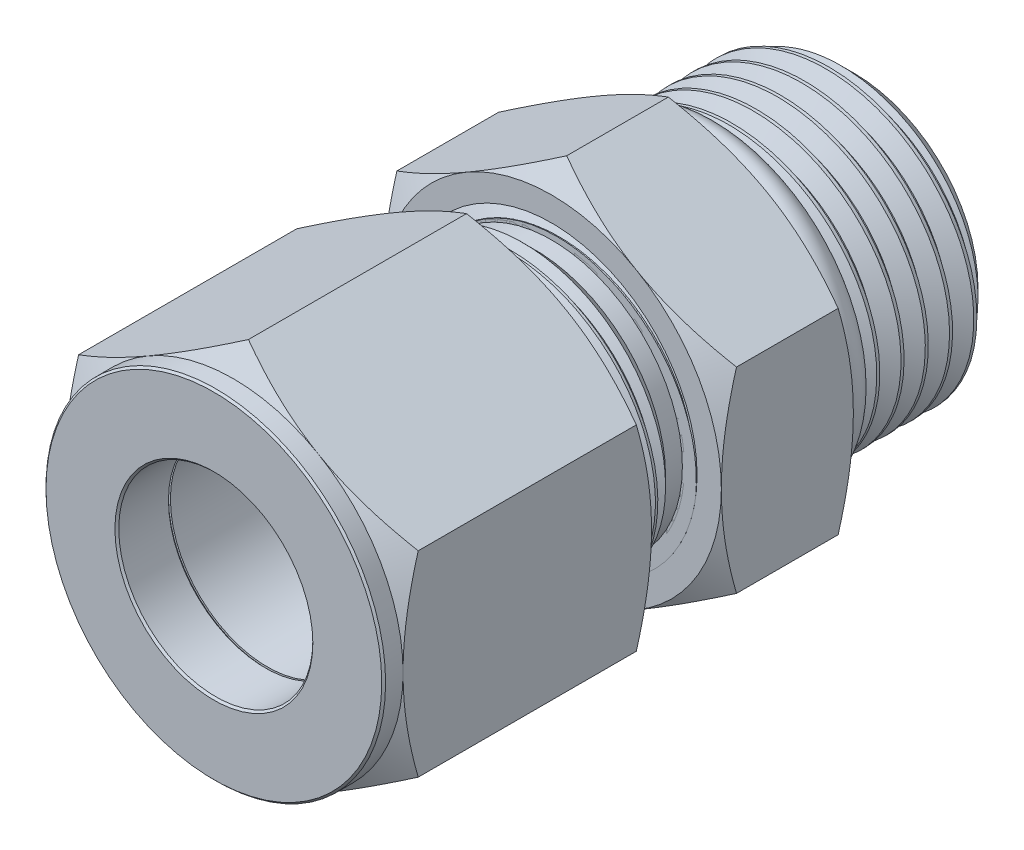
SolidWorks part; units mm, degrees
note: '?' marks a value the reader was unsure of.
material "AISI 316 Annealed Stainless Steel Bar (SS)"
ref_plane "Front Plane" through (0, 0, 0) normal (0, 0, 1) x (1, 0, 0)
ref_plane "Top Plane" through (0, 0, 0) normal (0, 1, 0) x (1, 0, 0)
ref_plane "Right Plane" through (0, 0, 0) normal (1, 0, 0) x (0, 0, -1)
sketch "Sketch1" plane through (0, 0, 0) normal (1, 0, 0) x (0, 0, -1)
  line L0 (0, 0) -> (41.91, 0) construction
  line L1 (0, 6.35) -> (0, -6.35) construction
  line L2 (17.526, 11.1125) -> (17.526, -11.1125) construction
  line L3 (7.0104, 9.525) -> (7.0104, -9.525) construction
  line L4 (7.0104, 9.525) -> (7.0104, 8.255) construction
  line L5 (30.734, 11.1125) -> (30.734, -11.1125) construction
  line L6 (6.1976, 8.6614) -> (13.5128, 6.8834) construction
  line L7 (13.5128, 6.8834) -> (13.5128, 6.35) construction
  line L8 (13.5128, 6.35) -> (7.3152, 6.35) construction
  line L9 (7.3152, 6.35) -> (6.1976, 7.4676) construction
  line L10 (6.1976, 7.4676) -> (6.1976, 8.6614) construction
  line L11 (3.5052, 7.8359) -> (4.7752, 7.8359) construction
  line L12 (4.7752, 7.8359) -> (4.7752, 7.4676) construction
  line L13 (4.7752, 7.4676) -> (6.1976, 7.4676) construction
  line L14 (30.734, 5.1562) -> (30.734, -5.1562) construction
  line L15 (6.1976, 7.4676) -> (6.1976, 6.35) construction
  line L16 (7.3152, 6.35) -> (3.5052, 6.35) construction
  line L17 (3.5052, 6.35) -> (3.5052, 7.8359) construction
  line L18 (6.1976, 6.35) -> (7.3152, 6.35) construction
  line L19 (0, 6.35) -> (3.5052, 6.35) construction
  line L20 (3.5052, 6.35) -> (7.0104, 6.35) construction
  line L21 (41.91, 9.525) -> (41.91, -9.525) construction
  line L22 (30.734, 9.525) -> (30.734, -9.525) construction
  line L23 (30.734, 9.525) -> (41.91, 9.525) construction
  line L24 (30.734, 9.525) -> (30.734, 7.9375) construction
  line L25 (31.8389, 10.3886) -> (31.8389, 8.1788) construction
  line L26 (41.91, 3.4163) -> (41.91, -3.4163) construction
  circle A0 centre (31.8389, 9.2837) radius 1.1049 construction
  point P4 (1.778, 0)
  point P10 (7.0104, 0)
  point P12 (17.526, 0)
  point P15 (22.098, 0)
  point P16 (10.16, 0)
  point P17 (22.86, 0)
  point P40 (30.734, 0)
  dimension "R" = 11.176
sketch "Sketch2" plane through (0, 0, 0) normal (0, 0, 1) x (1, 0, 0)
  line L0 (0, 6.35) -> (0, -6.35) construction
  line L1 (0, 12.8316) -> (-11.1125, 6.4158)
  line L2 (-11.1125, 6.4158) -> (-11.1125, -6.4158)
  line L3 (-11.1125, -6.4158) -> (0, -12.8316)
  line L4 (0, -12.8316) -> (11.1125, -6.4158)
  line L5 (11.1125, -6.4158) -> (11.1125, 6.4158)
  line L6 (11.1125, 6.4158) -> (0, 12.8316)
  line L7 (0, 12.8316) -> (0, 0) construction
  circle A0 centre (0, 0) radius 11.1125 construction
extrude "Boss-Extrude1" add sketch "Sketch2" against normal up to vertex (17.526 mm away) up to point (0, 0, -17.526)
sketch "Sketch3" plane through (0, 0, 0) normal (1, 0, 0) x (0, 0, -1)
  line L0 (0, 12.8316) -> (0, 11.1125)
  line L1 (0, 6.4158) -> (0, 12.8316) construction
  line L2 (0, 11.1125) -> (1.27, 11.1125)
  line L3 (1.27, 11.1125) -> (2.2625, 12.8316)
  line L4 (17.526, 12.8316) -> (0, 12.8316) construction
  line L5 (2.2625, 12.8316) -> (16.5335, 12.8316)
  line L6 (16.5335, 12.8316) -> (17.526, 11.1125)
  line L7 (17.526, 11.1125) -> (17.526, 12.8316)
  line L8 (17.526, 12.8316) -> (17.526, 14.5507)
  line L9 (17.526, 14.5507) -> (0, 14.5507)
  line L10 (0, 14.5507) -> (0, 12.8316)
  line L11 (0, 6.35) -> (0, 0)
  line L12 (0, 6.35) -> (0, -6.35) construction
  line L13 (0, 0) -> (17.526, 0)
  line L14 (17.526, 11.1125) -> (17.526, -11.1125) construction
  line L15 (17.526, 0) -> (17.526, 9.525)
  line L16 (17.526, 9.525) -> (7.0104, 9.525)
  line L17 (7.0104, 9.525) -> (7.0104, 8.255) construction
  line L18 (7.0104, 8.255) -> (3.5052, 8.255) construction
  line L19 (3.5052, 8.255) -> (3.5052, 6.35)
  line L20 (3.5052, 6.35) -> (0, 6.35)
  line L21 (3.5052, 8.255) -> (3.5052, 9.525) construction
  line L22 (3.5052, 9.525) -> (7.0104, 9.525) construction
  line L23 (7.0104, 8.89) -> (3.5052, 8.89)
  line L24 (3.5052, 8.89) -> (3.5052, 8.255)
  line L25 (7.0104, 8.89) -> (7.0104, 9.525)
  dimension "D1" = 30
  dimension "D2" = 1.27
revolve "Cut-Revolve1" cut sketch "Sketch3" angle 360 about L0
chamfer "Chamfer1" distance 0.127 angle 45 3 edges at (6.35, 0, -3.5052) (6.35, 0, 0) (11.1125, 0, 0)
sketch "Sketch4" plane through (0, 0, 0) normal (1, 0, 0) x (0, 0, -1)
  line L1 (30.734, 0) -> (10.16, 0)
  line L2 (30.734, 0) -> (30.734, 9.525)
  line L3 (30.734, 9.525) -> (10.16, 9.525)
  line L4 (10.16, 0) -> (10.16, 9.525)
  dimension "D1" = 20.574
revolve "Revolve1" add sketch "Sketch4" angle 360 about L1
sketch "Sketch7" plane through (0, 0, -30.734) normal (0, 0, -1) x (-1, 0, 0)
  line L0 (0, 0) -> (0, 12.8316) construction
  line L1 (0, 12.8316) -> (-11.1125, 6.4158)
  line L2 (-11.1125, 6.4158) -> (-11.1125, -6.4158)
  line L3 (-11.1125, -6.4158) -> (0, -12.8316)
  line L4 (0, -12.8316) -> (11.1125, -6.4158)
  line L5 (11.1125, -6.4158) -> (11.1125, 6.4158)
  line L6 (11.1125, 6.4158) -> (0, 12.8316)
  circle A0 centre (0, 0) radius 11.1125 construction
extrude "Boss-Extrude2" add sketch "Sketch7" against normal up to vertex (8.636 mm away) separate body up to point (0, 0, -22.098)
sketch "Sketch9" plane through (0, 0, 0) normal (1, 0, 0) x (0, 0, -1)
  line L0 (6.1976, 8.6614) -> (6.1976, 7.4676)
  line L1 (6.1976, 7.4676) -> (7.3152, 6.35)
  line L2 (7.3152, 6.35) -> (13.5128, 6.35)
  line L3 (13.5128, 6.35) -> (13.5128, 6.8834)
  line L4 (13.5128, 6.8834) -> (6.1976, 8.6614)
revolve "Revolve2" add sketch "Sketch9" angle 360 about L0
sketch "Sketch10" plane through (0, 0, 0) normal (1, 0, 0) x (0, 0, -1)
  line L0 (3.5052, 7.8359) -> (4.7752, 7.8359)
  line L1 (4.7752, 7.8359) -> (4.7752, 7.4676)
  line L2 (4.7752, 7.4676) -> (6.1976, 7.4676)
  line L4 (6.1976, 7.4676) -> (7.3152, 6.35)
  line L5 (7.3152, 6.35) -> (3.5052, 6.35)
  line L6 (3.5052, 6.35) -> (3.5052, 7.8359)
revolve "Revolve3" add sketch "Sketch10" angle 360 about L0
sketch "Sketch11" plane through (0, 0, 0) normal (1, 0, 0) x (0, 0, -1)
  line L0 (30.734, 0) -> (41.91, 0)
  line L1 (41.91, 0) -> (41.91, 9.525)
  line L2 (41.91, 9.525) -> (30.734, 9.525)
  line L3 (30.734, 9.525) -> (30.734, 0)
revolve "Revolve4" add sketch "Sketch11" angle 360 about L0
sketch "Sketch15" plane through (0, 0, 0) normal (1, 0, 0) x (0, 0, -1)
  line L0 (0, 0) -> (31.8389, 0) construction
  circle A0 centre (31.8389, 9.2837) radius 1.1049 construction
  circle A1 centre (31.8389, 9.2837) radius 1.1049
  point P3 (31.8389, 10.3886)
  point P7 (31.8389, -10.3886)
revolve "Revolve5" add sketch "Sketch15" angle 360 about L0
sketch "Sketch17" plane through (0, 0, -30.734) normal (0, 0, -1) x (-1, 0, 0)
  line L1 (11.1125, 6.4158) -> (0, 12.8316) construction
  line L2 (0, 12.8316) -> (-11.1125, 6.4158) construction
  line L3 (-11.1125, 6.4158) -> (-11.1125, -6.4158) construction
  line L4 (-11.1125, -6.4158) -> (0, -12.8316) construction
  line L5 (0, -12.8316) -> (11.1125, -6.4158) construction
  line L6 (11.1125, -6.4158) -> (11.1125, 6.4158) construction
  circle A0 centre (0, 0) radius 11.1125
extrude "Cut-Extrude1" cut sketch "Sketch17" against normal through all draft 60 flip side to cut
sketch "Sketch18" plane through (0, 0, -22.098) normal (0, 0, 1) x (1, 0, 0)
  circle A0 centre (0, 0) radius 11.1125 construction
  circle A1 centre (0, 0) radius 11.1125
extrude "Cut-Extrude2" cut sketch "Sketch18" against normal through all draft 60 flip side to cut
sketch "Sketch16" plane through (0, 0, 0) normal (1, 0, 0) x (0, 0, -1)
  line L0 (41.91, 0) -> (10.16, 0)
  line L1 (0, 0) -> (41.91, 0) construction
  line L2 (10.16, 0) -> (10.16, 7.6983)
  line L3 (6.1976, 8.6614) -> (13.5128, 6.8834) construction
  line L4 (10.16, 7.6983) -> (15.7074, 6.35)
  line L5 (15.7074, 6.35) -> (22.86, 6.35)
  line L6 (22.86, 6.35) -> (22.86, 5.1562)
  line L7 (22.86, 5.1562) -> (41.91, 5.1562)
  line L8 (41.91, 9.525) -> (41.91, -9.525) construction
  line L9 (41.91, 5.1562) -> (41.91, 0) construction
  line L10 (13.5128, 6.35) -> (7.3152, 6.35) construction
  line L11 (41.91, 5.1562) -> (43.4975, 5.1562)
  line L12 (43.4975, 5.1562) -> (43.4975, 0)
  line L13 (43.4975, 0) -> (41.91, 0)
  dimension "D1" = 1.5875
revolve "Cut-Revolve5" cut sketch "Sketch16" angle 360 about L0
combine bodies "Combine3" operation type add bodies to combine 106 115 114
chamfer "Chamfer2" distance 1.4287 angle 45 1 edges at (9.525, 0, -41.91)
sketch "Sketch5" plane through (0, 0, -10.16) normal (0, 0, -1) x (-1, 0, 0)
  circle A0 centre (0, 0) radius 9.525 construction
  circle A1 centre (0, 0) radius 9.525
  point P3 (0, 9.525)
curve "Helix/Spiral1" pitch 1.27 height 21.844 radius 9.525 centre (0, 0, -10.16) axis (0, 0, -1) start towards (0, 1, 0)
sketch "Sketch6" plane through (0, 0, 0) normal (1, 0, 0) x (0, 0, -1)
  line L0 (8.9694, 9.6625) -> (10.2394, 9.6625) construction
  line L1 (10.2394, 9.6625) -> (9.6044, 8.5626) construction
  line L2 (9.6044, 8.5626) -> (8.9694, 9.6625) construction
  line L3 (9.525, 8.7001) -> (9.6837, 8.7001) construction
  line L4 (9.0487, 9.525) -> (10.16, 9.525) construction
  line L5 (9.6044, 8.5626) -> (9.6044, 8.7001) construction
  line L6 (9.6044, 9.525) -> (9.6044, 9.6625) construction
  line L7 (9.525, 8.7001) -> (9.0091, 9.5937)
  line L8 (9.0091, 9.5937) -> (10.1997, 9.5937)
  line L9 (10.1997, 9.5937) -> (9.6837, 8.7001)
  line L10 (9.6837, 8.7001) -> (9.525, 8.7001)
  point P10 (9.6044, 9.5937)
  dimension "D1" = 1.27
  dimension "D2" = 0.1588
sweep "Cut-Sweep1" cut profiles "Sketch6" path "Helix/Spiral1" align with end faces yes
sketch "Sketch8" plane through (0, 0, 0) normal (1, 0, 0) x (0, 0, -1)
  line L0 (10.16, 9.6625) -> (10.16, 8.5626)
  line L1 (10.16, 8.5626) -> (11.2599, 9.6625)
  line L2 (11.2599, 9.6625) -> (10.16, 9.6625)
  line L3 (22.098, 9.6625) -> (19.8983, 9.6625)
  line L4 (19.8983, 9.6625) -> (20.9981, 8.5626)
  line L5 (20.9981, 8.5626) -> (22.098, 8.5626)
  line L6 (22.098, 8.5626) -> (22.098, 9.6625)
  line L7 (22.098, 11.1125) -> (23.0905, 12.8316) construction
  line L8 (22.098, 12.8316) -> (22.098, 6.4158) construction
  line L9 (23.0905, 12.8316) -> (29.7415, 12.8316) construction
  line L10 (23.0905, 12.8316) -> (29.7415, 12.8316) construction
  line L11 (22.86, 5.1562) -> (30.734, 5.1562) construction
  line L12 (29.7415, 12.8316) -> (30.734, 11.1125) construction
  line L14 (30.734, 12.8316) -> (30.734, 14.5507) construction
  line L15 (30.734, 14.5507) -> (22.098, 14.5507) construction
  line L16 (22.098, 14.5507) -> (22.098, 12.8316) construction
  line L17 (22.098, 12.8316) -> (22.098, 11.1125) construction
  line L18 (9.6044, 8.5626) -> (10.16, 8.5626) construction
  line L19 (10.2394, 9.6625) -> (10.16, 9.6625) construction
  line L20 (11.2599, 9.6625) -> (19.8983, 9.6625) construction
  line L21 (20.9981, 8.5626) -> (10.16, 8.5626) construction
  line L22 (10.16, 7.6983) -> (15.7074, 6.35) construction
  line L23 (30.734, 11.1125) -> (30.734, 12.8316) construction
  line L24 (10.16, 6.7352) -> (10.16, -8.7065) construction
  line L25 (6.1976, 8.6614) -> (13.5128, 6.8834) construction
  line L26 (30.734, 0) -> (10.16, 0) construction
  line L27 (10.16, 0) -> (10.16, 7.6983) construction
  line L28 (15.7074, 6.35) -> (22.86, 6.35) construction
  line L29 (22.86, 6.35) -> (22.86, 5.1562) construction
  line L30 (30.734, 5.1562) -> (30.734, 0) construction
  line L31 (22.86, 0) -> (22.86, 5.1562) construction
  dimension "D1" = 30
revolve "Cut-Revolve2" cut sketch "Sketch8" angle 360 about L0
ref_plane "Plane2" through (0, 0, -43.18) normal (0, 0, -1) x (-1, 0, 0)
sketch "Sketch12" plane through (0, 0, -43.18) normal (0, 0, -1) x (-1, 0, 0)
  circle A0 centre (0, 0) radius 9.525 construction
  circle A1 centre (0, 0) radius 8.0962
  circle A2 centre (0, 0) radius 8.0962
  point P0 (0, 9.525)
  dimension "D1" = 0
curve "Helix/Spiral2" pitch 1.5875 height 12.7635 turns 8.04
sketch "Sketch13" plane through (0, 0, 0) normal (1, 0, 0) x (0, 0, -1)
  line L0 (43.0808, 9.6969) -> (44.6683, 9.6969) construction
  line L1 (43.0808, 9.6969) -> (43.8745, 8.322) construction
  line L2 (43.8745, 8.322) -> (44.6683, 9.6969) construction
  line L3 (43.7753, 8.4939) -> (43.9737, 8.4939) construction
  line L4 (43.18, 9.525) -> (44.5691, 9.525) construction
  line L5 (43.8745, 8.322) -> (43.8745, 8.4939) construction
  line L6 (43.8745, 9.525) -> (43.8745, 9.6969) construction
  line L7 (43.8745, 9.6109) -> (44.6187, 9.6109) construction
  line L8 (43.8745, 8.322) -> (43.8745, -9.525) construction
  line L9 (43.8745, -9.525) -> (42.287, -9.525) construction
  line L10 (42.287, -9.525) -> (40.6995, -9.525) construction
  line L11 (40.6995, -9.525) -> (39.112, -9.525) construction
  line L12 (43.0808, 9.6969) -> (44.6187, 9.6109)
  line L13 (44.6187, 9.6109) -> (43.9737, 8.4939)
  line L14 (43.9737, 8.4939) -> (43.7753, 8.4939)
  line L15 (43.7753, 8.4939) -> (43.0808, 9.6969)
  line L16 (30.734, -9.525) -> (40.4812, -9.525) construction
  line L17 (39.112, -9.525) -> (37.5245, -9.525) construction
  line L18 (37.5245, -9.525) -> (35.937, -9.525) construction
  dimension "D1" = 1.5875
  dimension "D2" = 0.1984
sweep "Cut-Sweep2" cut profiles "Sketch13" path "Helix/Spiral2" align with end faces yes
ref_plane "Plane1" through (-2.3688, 9.2257, -31.8064) normal (-0.9682, -0.2486, 0.0269) x (0.2495, -0.953, 0.1719)
sketch "Sketch14" plane through (0, 0, 0) normal (1, 0, 0) x (0, 0, -1)
  line L0 (43.8745, 8.322) -> (41.91, 8.322) construction
  line L1 (33.4836, 9.6969) -> (30.734, 9.6969)
  line L2 (41.91, 0) -> (30.734, 0) construction
  line L3 (41.91, 0) -> (41.91, 5.1562) construction
  line L4 (41.91, 5.1562) -> (30.734, 5.1562) construction
  line L5 (41.91, 9.525) -> (41.91, -9.525) construction
  line L6 (41.91, 8.322) -> (40.5352, 9.6969) construction
  line L7 (40.5352, 9.6969) -> (41.91, 9.6969) construction
  line L8 (41.91, 9.6969) -> (41.91, 8.322) construction
  line L9 (43.0808, 9.6969) -> (44.6683, 9.6969) construction
  line L10 (30.734, 0) -> (30.734, 5.1562) construction
  line L11 (30.734, 9.6969) -> (30.734, 8.322)
  line L12 (30.734, 8.322) -> (32.1088, 8.322)
  line L13 (32.1088, 8.322) -> (33.4836, 9.6969)
  line L14 (33.4836, 9.6969) -> (40.5352, 9.6969) construction
  line L15 (41.91, 8.322) -> (32.1088, 8.322) construction
  line L17 (30.734, 11.1125) -> (30.734, -11.1125) construction
revolve "Cut-Revolve4" cut sketch "Sketch14" angle 360 about L0
sketch "Sketch19" plane through (0, 0, 0) normal (1, 0, 0) x (0, 0, -1)
  line L5 (22.098, 9.6237) -> (22.098, 0) construction
  line L8 (22.098, 9.525) -> (30.734, 9.525)
  line L9 (22.098, 9.525) -> (22.098, 8.7001)
  line L10 (22.098, 8.7001) -> (30.734, 8.7001)
  line L11 (30.734, 9.525) -> (30.734, 8.7001)
  line L12 (30.734, 11.1125) -> (30.734, -11.1125) construction
revolve "Cut-Revolve7" cut sketch "Sketch19" angle 360 about L0
ref_axis "Center Axis 1" through (0, 0, -30.734) along (0, 0, -1)?
ref_plane "Contact Plane 1" through (0, 0, 0) normal (0, 0, 1) x (1, 0, 0)
ref_plane "Contact Plane 2" through (0, 0, -41.91) normal (0, 0, -1) x (-1, 0, 0)
equation "\"D4@Helix/Spiral1\" = \"Straight Thread Pitch@Sketch1\""
equation "\"D3@Helix/Spiral1\" = \"D4@Helix/Spiral1\" + \"D1@Sketch4\""
equation "\"D1@Sketch6\" = \"D4@Helix/Spiral1\""
equation "\"D2@Sketch6\" = \"D1@Sketch6\" / 8"
equation "\"D4@Helix/Spiral2\" = \"Thread Pitch@Sketch1\""
equation "\"D3@Helix/Spiral2\" = \"D4@Helix/Spiral2\" + \"R@Sketch1\""
equation "\"D1@Sketch13\" = \"D4@Helix/Spiral2\""
equation "\"D2@Sketch13\" = \"D1@Sketch13\" / 8"
